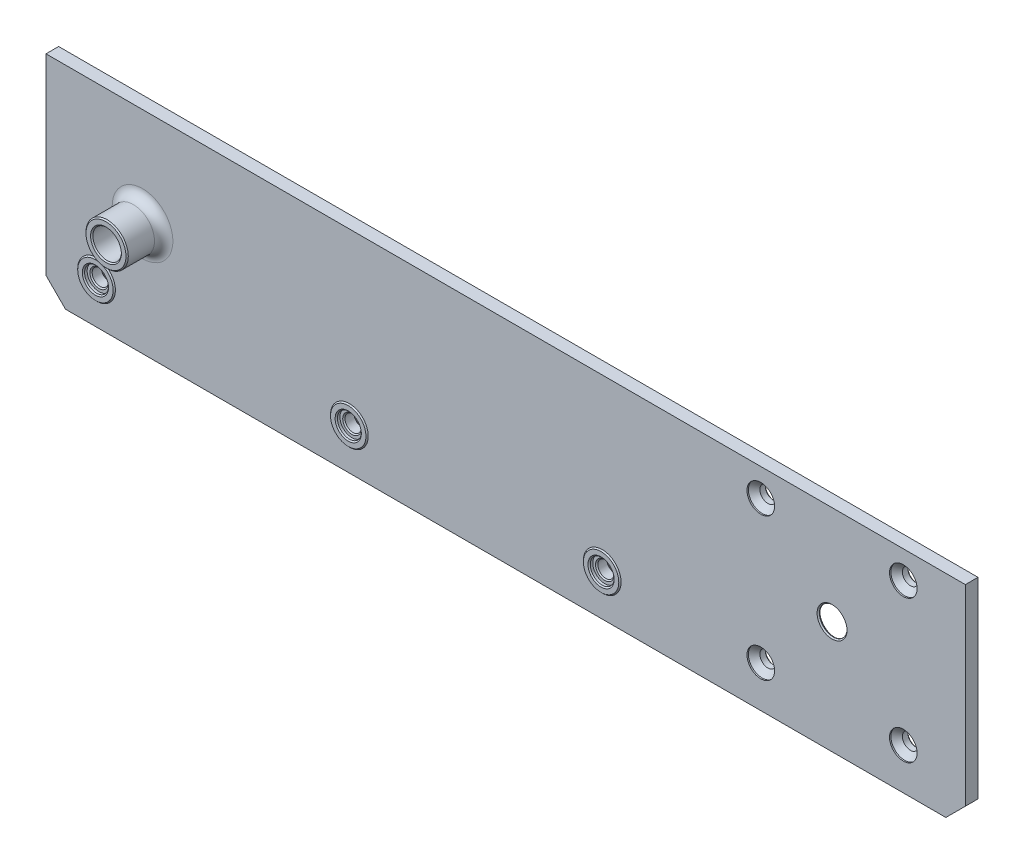
SolidWorks part; units mm, degrees
ref_plane "Front Plane" through (0, 0, 0) normal (0, 0, 1) x (1, 0, 0)
ref_plane "Top Plane" through (0, 0, 0) normal (0, 1, 0) x (1, 0, 0)
ref_plane "Right Plane" through (0, 0, 0) normal (1, 0, 0) x (0, 0, -1)
sketch "Sketch1" plane through (0, 0, 0) normal (0, 0, 1) x (1, 0, 0)
  line L0 (-171, 21.5) -> (29, 21.5)
  line L1 (29, 21.5) -> (29, -20.2574)
  line L2 (29, -20.2574) -> (24.7574, -24.5)
  line L3 (24.7574, -24.5) -> (-166.7574, -24.5)
  line L4 (-166.7574, -24.5) -> (-171, -20.2574)
  line L5 (-171, -20.2574) -> (-171, 21.5)
  line L6 (-14.5858, 21) -> (14.5858, 21) construction
  line L7 (21, 14.5858) -> (21, -14.5858) construction
  line L8 (14.5858, -21) -> (-14.5858, -21) construction
  circle A0 centre (15.5, 15.5) radius 1.75
  circle A1 centre (-15.5, 15.5) radius 1.75
  circle A2 centre (15.5, -15.5) radius 1.75
  circle A3 centre (-15.5, -15.5) radius 1.75
  circle A4 centre (0, 0) radius 3
  dimension "D1" = 3.5
  dimension "D8" = 6
  dimension "D2" = 0.5
  dimension "D3" = 8
  dimension "D4" = 135
  dimension "D5" = 6
  dimension "D6" = 3.5
  dimension "D7" = 200
extrude "Boss-Extrude1" add sketch "Sketch1" along normal blind 3
sketch "Sketch2" plane through (0, 0, 0) normal (0, 0, -1) x (-1, 0, 0)
  circle A2 centre (0, 0) radius 11.45
  circle A3 centre (0, 0) radius 11.45
  dimension "D1" = 0.2
extrude "Cut-Extrude1" cut sketch "Sketch2" against normal blind 2.4
sketch "Sketch3" plane through (0, 0, 3) normal (0, 0, 1) x (1, 0, 0)
  line L0 (15.5, -15.5) -> (-15.5, -15.5) construction
  line L1 (-160, -15.5) -> (-105, -15.5) construction
  line L2 (-105, -15.5) -> (-50, -15.5) construction
  circle A0 centre (-50, -15.5) radius 1.75
  circle A1 centre (-105, -15.5) radius 1.75
  circle A2 centre (-160, -15.5) radius 1.75
  dimension "D2" = 3.5
  dimension "D1" = 50
  dimension "D3" = 55
extrude "Cut-Extrude2" cut sketch "Sketch3" against normal up to next
sketch "Sketch4" plane through (0, 0, 3) normal (0, 0, 1) x (1, 0, 0)
  circle A0 centre (-50, -15.5) radius 2.6
  circle A1 centre (-105, -15.5) radius 2.6
  circle A2 centre (-160, -15.5) radius 2.6
  dimension "D1" = 5.2
extrude "Cut-Extrude3" cut sketch "Sketch4" against normal blind 0.55
sketch "Sketch5" plane through (0, 0, 3) normal (0, 0, 1) x (1, 0, 0)
  circle A0 centre (-150, 0) radius 3.1
  point P2 (0, 0)
  dimension "D1" = 6.2
  dimension "D2" = 150
extrude "Cut-Extrude4" cut sketch "Sketch5" against normal up to next
sketch "Sketch6" plane through (0, 0, 3) normal (0, 0, 1) x (1, 0, 0)
  circle A0 centre (-150, 0) radius 3.1 construction
  circle A1 centre (-150, 0) radius 3.1
  circle A2 centre (-150, 0) radius 4.6
  point P4 (-150, -3.1)
  point P5 (-150, -4.6)
  dimension "D1" = 1.5
extrude "Boss-Extrude2" add sketch "Sketch6" along normal blind 7.95
sketch "Sketch7" plane through (0, 0, 3) normal (0, 0, 1) x (1, 0, 0)
  circle A0 centre (-50, -15.5) radius 2.6 construction
  circle A1 centre (-105, -15.5) radius 2.6 construction
  circle A2 centre (-50, -15.5) radius 2.6
  circle A3 centre (-105, -15.5) radius 2.6
  circle A4 centre (-50, -15.5) radius 3.6
  circle A5 centre (-105, -15.5) radius 3.6
  circle A6 centre (-160, -15.5) radius 2.6 construction
  circle A7 centre (-160, -15.5) radius 2.6
  circle A8 centre (-160, -15.5) radius 3.6
  point P8 (-50, -18.1)
  point P9 (-50, -19.1)
  dimension "D1" = 1
extrude "Boss-Extrude3" add sketch "Sketch7" along normal mid plane 0.5
hole_wizard "CSK for M3 Flat Head Machine Screw1" positions "Sketch8" profile "Sketch9" countersink size "M3" standard "ANSI Metric" end condition through all
sketch "Sketch8" plane through (0, 0, 3) normal (0, 0, 1) x (1, 0, 0)
  point P0 (-15.5, 15.5)
  point P3 (15.5, 15.5)
  point P6 (15.5, -15.5)
  point P9 (-15.5, -15.5)
sketch "Sketch9" plane through (-15.5, 15.5, 3) normal (1, 0, 0) x (0, -1, 0)
  line L0 (0, 0) -> (0, 3)
  line L1 (0, 3) -> (1.75, 3)
  line L2 (1.75, 3) -> (1.75, 1.55)
  line L3 (1.75, 1.55) -> (3, 0.3)
  line L4 (3, 0.3) -> (3, 0)
  line L6 (3, 0) -> (0, 0)
  line L7 (-1.75, 1.55) -> (-3, 0.3) construction
  line L11 (0, -6.35) -> (0, 107.95) construction
  dimension "Thru Hole Dia." = 3.5
  dimension "Thru Hole Depth" = 3
  dimension "C'Sink Dia." = 6
  dimension "C'Sink Angle" = 90
  dimension "Head Clearance" = 0.3
fillet "Fillet1" radius 2 1 edges at (-145.4, 0, 3)
chamfer "Chamfer1" distance 0.5 angle 45 3 edges at (-53.6, -15.5, 3) (-108.6, -15.5, 3) (-163.6, -15.5, 3)
chamfer "Chamfer2" distance 0.25 angle 45 26 edges at (-11.45, 0, 2.4) (-3, 0, 2.4) (-51.75, -15.5, 0) (-106.75, -15.5, 0) (-11.45, 0, 0) (-13.75, -15.5, 0) (-13.75, 15.5, 0) (-71, 21.5, 0) (-171, 0.6213, 0) (-168.8787, -22.3787, 0) (-71, -24.5, 0) (26.8787, -22.3787, 0) (29, 0.6213, 0) (17.25, 15.5, 0) (17.25, -15.5, 0) (-146.9, 0, 10.95) (-145.4, 0, 10.95) (3, 0, 3) (-48.25, -15.5, 2.45) (-103.25, -15.5, 2.45) (-47.4, -15.5, 3.25) (-102.4, -15.5, 3.25) (-153.1, 0, 0) (-161.75, -15.5, 0) (-158.25, -15.5, 2.45) (-157.4, -15.5, 3.25)
